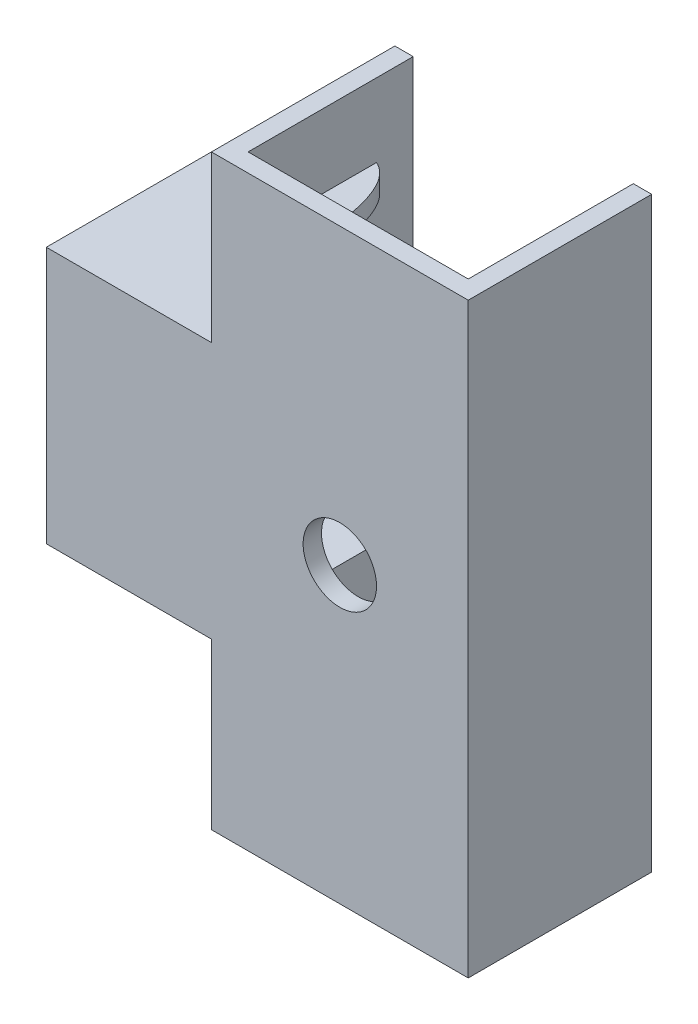
SolidWorks part; units mm, degrees
ref_plane "Alzado" through (0, 0, 0) normal (0, 0, 1) x (1, 0, 0)
ref_plane "Planta" through (0, 0, 0) normal (0, 1, 0) x (1, 0, 0)
ref_plane "Vista lateral" through (0, 0, 0) normal (1, 0, 0) x (0, 0, -1)
sketch "Croquis1" plane through (0, 0, 0) normal (0, 0, 1) x (1, 0, 0)
  line L0 (117743.4169, 152337.8366) -> (131743.4169, 152337.8366)
  line L1 (131743.4169, 152337.8366) -> (131743.4169, 161337.8366)
  line L2 (131743.4169, 161337.8366) -> (140743.4169, 161337.8366)
  line L3 (140743.4169, 161337.8366) -> (140743.4169, 175337.8366)
  line L4 (140743.4169, 175337.8366) -> (117743.4169, 175337.8366)
  line L5 (117743.4169, 175337.8366) -> (117743.4169, 152337.8366)
  line L6 (118743.4169, 152337.8366) -> (118743.4169, 166437.8366)
  line L7 (118743.4169, 174337.8366) -> (122843.4169, 174337.8366)
  line L8 (130743.4169, 152337.8366) -> (130743.4169, 162337.8366)
  line L9 (140743.4169, 162337.8366) -> (130743.4169, 162337.8366)
  line L10 (131743.4169, 161337.8366) -> (108743.4169, 161337.8366)
  line L11 (108743.4169, 161337.8366) -> (108743.4169, 162337.8366)
  line L12 (108743.4169, 162337.8366) -> (122843.4169, 162337.8366)
  line L13 (131743.4169, 161337.8366) -> (131743.4169, 184337.8366)
  line L14 (131743.4169, 184337.8366) -> (130743.4169, 184337.8366)
  line L15 (130743.4169, 184337.8366) -> (130743.4169, 170237.8366)
  line L16 (118743.4169, 174337.8366) -> (118743.4169, 184337.8366)
  line L17 (118743.4169, 184337.8366) -> (117743.4169, 184337.8366)
  line L18 (117743.4169, 184337.8366) -> (117743.4169, 175337.8366)
  line L19 (118743.4169, 174337.8366) -> (108743.4169, 174337.8366)
  line L20 (108743.4169, 174337.8366) -> (108743.4169, 175337.8366)
  line L21 (108743.4169, 175337.8366) -> (117743.4169, 175337.8366)
  line L22 (108743.4169, 174337.8366) -> (108743.4169, 162337.8366)
  line L23 (118743.4169, 184337.8366) -> (130743.4169, 184337.8366)
  line L24 (122743.4169, 174237.8366) -> (122743.4169, 172837.8366)
  line L25 (124243.4169, 171337.8366) -> (125243.4169, 171337.8366)
  line L26 (126743.4169, 172837.8366) -> (126743.4169, 174237.8366)
  line L27 (118843.4169, 170337.8366) -> (120243.4169, 170337.8366)
  line L28 (121743.4169, 168837.8366) -> (121743.4169, 167837.8366)
  line L29 (120243.4169, 166337.8366) -> (118843.4169, 166337.8366)
  line L30 (130643.4169, 170337.8366) -> (129243.4169, 170337.8366)
  line L31 (127743.4169, 168837.8366) -> (127743.4169, 167837.8366)
  line L32 (129243.4169, 166337.8366) -> (130643.4169, 166337.8366)
  line L33 (122743.4169, 162437.8366) -> (122743.4169, 163837.8366)
  line L34 (124243.4169, 165337.8366) -> (125243.4169, 165337.8366)
  line L35 (126743.4169, 163837.8366) -> (126743.4169, 162337.8366)
  line L36 (121743.4169, 168337.8366) -> (127743.4169, 168337.8366) construction
  line L37 (118743.4169, 170237.8366) -> (120243.4169, 170237.8366)
  line L38 (118843.4169, 174237.8366) -> (122743.4169, 174237.8366)
  line L39 (121643.4169, 168837.8366) -> (121643.4169, 167837.8366)
  line L40 (118843.4169, 162437.8366) -> (118843.4169, 166337.8366)
  line L41 (118843.4169, 162437.8366) -> (122743.4169, 162437.8366)
  line L42 (130643.4169, 174237.8366) -> (130643.4169, 170337.8366)
  line L43 (120243.4169, 166437.8366) -> (118743.4169, 166437.8366)
  line L44 (118743.4169, 174237.8366) -> (140743.4169, 174237.8366) construction
  line L45 (122843.4169, 162337.8366) -> (122843.4169, 163837.8366)
  line L46 (124243.4169, 165237.8366) -> (125243.4169, 165237.8366)
  line L47 (126643.4169, 163837.8366) -> (126643.4169, 162337.8366)
  line L48 (130743.4169, 170237.8366) -> (129243.4169, 170237.8366)
  line L49 (127843.4169, 168837.8366) -> (127843.4169, 167837.8366)
  line L50 (129243.4169, 166437.8366) -> (130743.4169, 166437.8366)
  line L51 (122843.4169, 174337.8366) -> (122843.4169, 172837.8366)
  line L52 (124243.4169, 171437.8366) -> (125243.4169, 171437.8366)
  line L53 (126643.4169, 172837.8366) -> (126643.4169, 174337.8366)
  line L54 (130643.4169, 166337.8366) -> (130643.4169, 162437.8366)
  line L55 (130743.4169, 166437.8366) -> (130743.4169, 162337.8366)
  line L56 (129243.4169, 166337.8366) -> (130743.4169, 166337.8366) construction
  line L57 (130743.4169, 170337.8366) -> (129243.4169, 170337.8366) construction
  line L58 (126643.4169, 174337.8366) -> (140743.4169, 174337.8366)
  line L59 (118743.4169, 174337.8366) -> (140743.4169, 174337.8366) construction
  line L60 (126743.4169, 174237.8366) -> (130643.4169, 174237.8366)
  line L61 (126743.4169, 172837.8366) -> (126743.4169, 174337.8366) construction
  line L62 (122743.4169, 174337.8366) -> (122743.4169, 172837.8366) construction
  line L63 (118743.4169, 170237.8366) -> (118743.4169, 174337.8366)
  line L64 (118843.4169, 170337.8366) -> (118843.4169, 174237.8366)
  line L65 (118743.4169, 170337.8366) -> (120243.4169, 170337.8366) construction
  line L66 (120243.4169, 166337.8366) -> (118743.4169, 166337.8366) construction
  line L67 (126743.4169, 162437.8366) -> (130643.4169, 162437.8366)
  line L68 (122743.4169, 162337.8366) -> (122743.4169, 163837.8366) construction
  line L69 (126643.4169, 162337.8366) -> (130743.4169, 162337.8366)
  arc A0 (125243.4169, 165337.8366) -> (126743.4169, 163837.8366) centre (125243.4169, 163837.8366) cw
  arc A1 (122743.4169, 163837.8366) -> (124243.4169, 165337.8366) centre (124243.4169, 163837.8366) cw
  arc A2 (127743.4169, 167837.8366) -> (129243.4169, 166337.8366) centre (129243.4169, 167837.8366) ccw
  arc A3 (129243.4169, 170337.8366) -> (127743.4169, 168837.8366) centre (129243.4169, 168837.8366) ccw
  arc A4 (125243.4169, 171337.8366) -> (126743.4169, 172837.8366) centre (125243.4169, 172837.8366) ccw
  arc A5 (122743.4169, 172837.8366) -> (124243.4169, 171337.8366) centre (124243.4169, 172837.8366) ccw
  arc A6 (120243.4169, 170337.8366) -> (121743.4169, 168837.8366) centre (120243.4169, 168837.8366) cw
  arc A7 (121743.4169, 167837.8366) -> (120243.4169, 166337.8366) centre (120243.4169, 167837.8366) cw
  circle A8 centre (124743.4169, 168337.8366) radius 2000
  arc A9 (120243.4169, 170237.8366) -> (121643.4169, 168837.8366) centre (120243.4169, 168837.8366) cw
  arc A10 (121643.4169, 167837.8366) -> (120243.4169, 166437.8366) centre (120243.4169, 167837.8366) cw
  arc A11 (122843.4169, 163837.8366) -> (124243.4169, 165237.8366) centre (124243.4169, 163837.8366) cw
  arc A12 (125243.4169, 165237.8366) -> (126643.4169, 163837.8366) centre (125243.4169, 163837.8366) cw
  arc A13 (129243.4169, 170237.8366) -> (127843.4169, 168837.8366) centre (129243.4169, 168837.8366) ccw
  arc A14 (127843.4169, 167837.8366) -> (129243.4169, 166437.8366) centre (129243.4169, 167837.8366) ccw
  arc A15 (122843.4169, 172837.8366) -> (124243.4169, 171437.8366) centre (124243.4169, 172837.8366) ccw
  arc A16 (125243.4169, 171437.8366) -> (126643.4169, 172837.8366) centre (125243.4169, 172837.8366) ccw
  circle A17 centre (124743.4169, 168337.8366) radius 1900
  point P34 (126743.4169, 163087.8366)
  point P39 (126743.4169, 165337.8366)
  point P42 (122743.4169, 165337.8366)
  point P45 (127743.4169, 166337.8366)
  point P48 (127743.4169, 170337.8366)
  point P51 (126743.4169, 171337.8366)
  point P54 (122743.4169, 171337.8366)
  point P57 (121743.4169, 170337.8366)
  point P60 (121743.4169, 166337.8366)
  point P105 (0, 0)
  dimension "D21" = 1500
  dimension "D22" = 4000
  dimension "D1" = 12000
  dimension "D2" = 1000
  dimension "D3" = 1000
  dimension "D4" = 1000
  dimension "D5" = 1000
  dimension "D6" = 12000
  dimension "D7" = 9000
  dimension "D8" = 9000
  dimension "D9" = 9000
  dimension "D10" = 9000
  dimension "D11" = 4000
  dimension "D12" = 4000
  dimension "D13" = 4000
  dimension "D14" = 4000
  dimension "D18" = 4000
  dimension "D19" = 4000
  dimension "D20" = 3000
  dimension "D23" = 100
  dimension "D24" = 100
  dimension "D25" = 100
  dimension "D26" = 100
ref_plane "Plano1" through (0, 161337.8366, 0) normal (0, 1, 0) x (1, 0, 0)
ref_plane "Plano2" through (0, 175337.8366, 0) normal (0, 1, 0) x (1, 0, 0)
ref_plane "Plano3" through (117743.4169, 0, 0) normal (1, 0, 0) x (0, 0, -1)
ref_plane "Plano4" through (131743.4169, 0, 0) normal (1, 0, 0) x (0, 0, -1)
ref_plane "Plano5" through (113243.4169, 0, 0) normal (1, 0, 0) x (0, 0, -1)
ref_plane "Plano6" through (0, 179837.8366, 0) normal (0, 1, 0) x (1, 0, 0)
ref_plane "Plano7" through (136243.4169, 0, 0) normal (1, 0, 0) x (0, 0, -1)
ref_plane "Plano8" through (0, 156837.8366, 0) normal (0, 1, 0) x (1, 0, 0)
sketch "Croquis2" plane through (0, 156837.8366, 0) normal (0, 1, 0) x (1, 0, 0)
  line L0 (117743.4169, 0) -> (131743.4169, 0) construction
  line L1 (117743.4169, 0) -> (131743.4169, 0)
  line L2 (131743.4169, 0) -> (131743.4169, 8000)
  line L3 (131743.4169, 8000) -> (130743.4169, 8000)
  line L4 (130743.4169, 8000) -> (130743.4169, 1000)
  line L5 (130743.4169, 1000) -> (118743.4169, 1000)
  line L6 (118743.4169, 1000) -> (118743.4169, 8000)
  line L7 (118743.4169, 8000) -> (117743.4169, 8000)
  line L8 (117743.4169, 8000) -> (117743.4169, 0)
  spline S0 degree 2 poles (130743.4169, 8000) (128761.6752, 7234.3483) (128743.4169, 1000) knots 0 0 0 0.590989 0.590989 0.590989
  spline S1 degree 2 poles (118743.4169, 8000) (120739.8111, 7120.5788) (120743.4169, 1000) knots 0 0 0 0.514461 0.514461 0.514461
  point P10 (0, 0)
  dimension "D1" = 1000
  dimension "D2" = 1000
  dimension "D3" = 1000
  dimension "D4" = 7000
  dimension "D5" = 7000
  dimension "D6" = 2000
  dimension "D7" = 2000
sketch "Croquis3" plane through (0, 179837.8366, 0) normal (0, 1, 0) x (1, 0, 0)
  line L0 (118743.4169, 1000) -> (118743.4169, 8000) construction
  line L1 (130743.4169, 1000) -> (118743.4169, 1000) construction
  line L2 (130743.4169, 8000) -> (130743.4169, 1000) construction
  line L3 (118743.4169, 1000) -> (118743.4169, 8000)
  line L4 (130743.4169, 1000) -> (118743.4169, 1000)
  line L5 (130743.4169, 8000) -> (130743.4169, 1000)
  parabola Q0 (118743.4169, 8000) -> (120743.4169, 1000) focus (118361.6774, 7241.9739) apex (118662.5082, 8033.1777) construction
  parabola Q1 (130743.4169, 8000) -> (128743.4169, 1000) focus (131040.6578, 7282.3326) apex (130778.3168, 8013.005) construction
  parabola Q2 (118743.4169, 8000) -> (120743.4169, 1000) focus (118361.6774, 7241.9739) apex (118662.5082, 8033.1777)
  parabola Q3 (130743.4169, 8000) -> (128743.4169, 1000) focus (131040.6578, 7282.3326) apex (130778.3168, 8013.005)
sketch "Croquis4" plane through (113243.4169, 0, 0) normal (1, 0, 0) x (0, 0, -1)
  line L0 (0, 174337.8366) -> (0, 162337.8366) construction
  line L1 (0, 174337.8366) -> (0, 162337.8366)
  line L2 (0, 162337.8366) -> (8000, 162337.8366)
  line L3 (0, 174337.8366) -> (8000, 174337.8366)
  spline S0 degree 2 poles (8000, 162337.8366) (6698.659, 164240.8241) (0, 164337.8366) knots 0 0 0 0.70753 0.70753 0.70753
  spline S1 degree 2 poles (8000, 174337.8366) (6599.8546, 172118.7435) (0, 172337.8366) knots 0 0 0 0.648378 0.648378 0.648378
  dimension "D1" = 8000
  dimension "D2" = 2000
  dimension "D3" = 2000
sketch "Croquis5" plane through (136243.4169, 0, 0) normal (1, 0, 0) x (0, 0, -1)
  line L0 (0, 162337.8366) -> (8000, 162337.8366) construction
  line L1 (0, 174337.8366) -> (0, 162337.8366) construction
  line L2 (0, 174337.8366) -> (8000, 174337.8366) construction
  line L3 (0, 162337.8366) -> (8000, 162337.8366)
  line L4 (0, 174337.8366) -> (0, 162337.8366)
  line L5 (0, 174337.8366) -> (8000, 174337.8366)
  parabola Q0 (8000, 162337.8366) -> (0, 164337.8366) focus (7402.6379, 161620.0634) apex (8222.0253, 161894.2353) construction
  parabola Q1 (8000, 174337.8366) -> (0, 172337.8366) focus (7073.338, 175098.4045) apex (8142.0414, 174597.2807) construction
  parabola Q2 (8000, 162337.8366) -> (0, 164337.8366) focus (7402.6379, 161620.0634) apex (8222.0253, 161894.2353)
  parabola Q3 (8000, 174337.8366) -> (0, 172337.8366) focus (7073.338, 175098.4045) apex (8142.0414, 174597.2807)
extrude "Saliente-Extruir1" add sketch "Croquis1" against normal blind 1000 contours L15 L58 L13 L4 | L14 L15 L4 L13 | L23 L16 L4 L15 | L17 L18 L4 L16 | L19 L16 L4 L5 | L21 L20 L19 L5 | L19 L22 L12 L5 | L12 L11 L10 L5 | L12 L5 L10 L6 | L6 L10 L5 L0 | L8 L10 L6 L0 | L1 L10 L8 L0 | L10 L13 L9 L8 | A12 L46 A11 L45 L12 L6 L10 L8 L69 L47 | L49 A14 L50 L55 L9 L13 L58 L15 L48 A13 | L52 A16 L53 L58 L15 L4 L16 L7 L51 A15 | A10 L39 A9 L37 L63 L19 L5 L12 L6 L43 | L28 A7 L29 L40 L41 L33 A1 L34 A0 L35 L67 L54 L32 A2 L31 A3 L30 L42 L60 L26 A4 L25 A5 L24 L38 L64 L27 A6 A8 | A16 L52 A15 L51 L7 L63 L37 A9 L39 A10 L43 L6 L12 L45 A11 L46 A12 L47 L69 L35 A0 L34 A1 L33 L41 L40 L29 A7 L28 A6 L27 L64 L38 L24 A5 L25 A4 L26 L60 L42 L30 A3 L31 A2 L32 L54 L67 L55 region at (118243.4169, 156837.8366, 0) region at (124743.4169, 156837.8366, 0) region at (113243.4169, 161837.8366, 0) region at (118243.4169, 161837.8366, 0) region at (131243.4169, 156837.8366, 0) region at (124743.4169, 162689.636, 0) region at (113243.4169, 168337.8366, 0) region at (119095.2163, 168337.8366, 0) region at (131243.4169, 161837.8366, 0) region at (126910.2941, 163137.8366, 0) region at (118760.3875, 164387.8366, 0) region at (113243.4169, 174837.8366, 0) region at (118243.4169, 174837.8366, 0) region at (130391.6175, 168337.8366, 0) region at (118243.4169, 179837.8366, 0) region at (124743.4169, 173986.0372, 0) region at (124743.4169, 179837.8366, 0) region at (131243.4169, 174837.8366, 0) region at (131243.4169, 179837.8366, 0)
extrude "Saliente-Extruir2" add sketch "Croquis1<6>" against normal blind 10000 contours L15 L58 L13 L4 | L14 L15 L4 L13 | L17 L18 L4 L16 | L19 L16 L4 L5 | L21 L20 L19 L5 | L12 L11 L10 L5 | L12 L5 L10 L6 | L6 L10 L5 L0 | L1 L10 L8 L0 | L10 L13 L9 L8 | L49 A14 L50 L55 L9 L13 L58 L15 L48 A13 region at (118243.4169, 156837.8366, 0) region at (113243.4169, 161837.8366, 0) region at (118243.4169, 161837.8366, 0) region at (131243.4169, 156837.8366, 0) region at (131243.4169, 161837.8366, 0) region at (113243.4169, 174837.8366, 0) region at (118243.4169, 174837.8366, 0) region at (130391.6175, 168337.8366, 0) region at (118243.4169, 179837.8366, 0) region at (131243.4169, 174837.8366, 0) region at (131243.4169, 179837.8366, 0)
sketch "Croquis1<6>" plane through (0, 0, 0) normal (0, 0, 1) x (1, 0, 0) same geometry as "Croquis1"
extrude "Saliente-Extruir3" add sketch "Croquis2" along normal blind 500 and the other way blind 500 contours L4 S0 L5 | S1 L6 L5 region at (119605.9639, 156837.8366, -3955.1574) region at (129880.6924, 156837.8366, -3967.5864)
extrude "Saliente-Extruir4" add sketch "Croquis3" along normal blind 500 and the other way blind 500 contours Q2 L3 L4 | L5 Q3 L4 region at (129880.6924, 179837.8366, -3967.5864) region at (119605.9639, 179837.8366, -3955.1574)
extrude "Saliente-Extruir5" add sketch "Croquis4" along normal blind 500 and the other way blind 500 contours L2 S0 L1 | S1 L3 L1 region at (113243.4169, 173449.622, -3378.0839) region at (113243.4169, 163181.6256, -3312.204)
